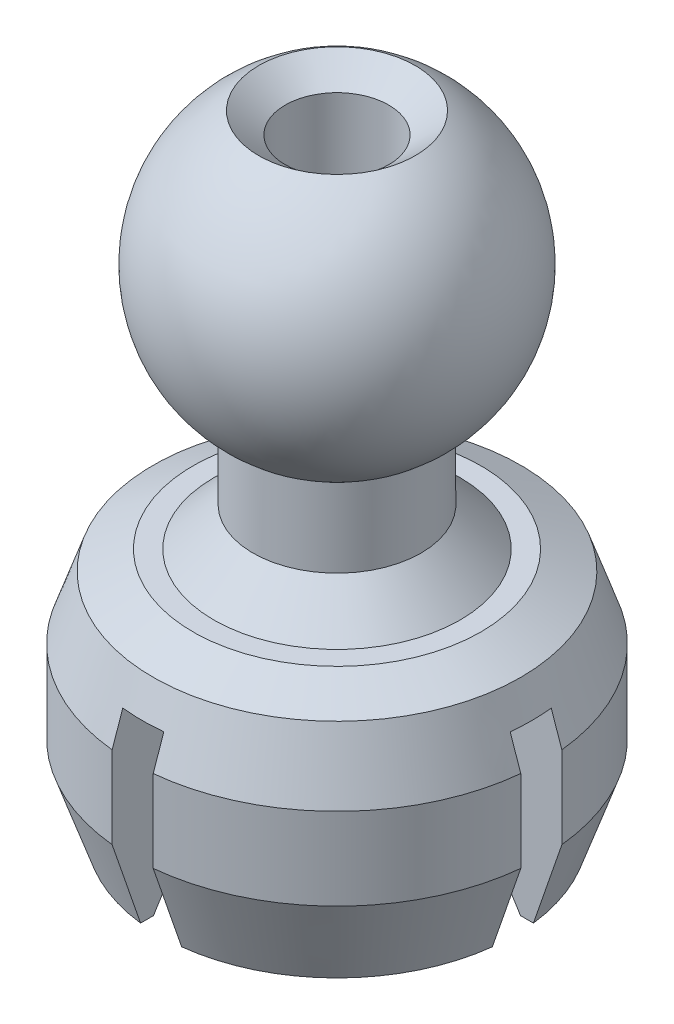
SolidWorks part; units mm, degrees
ref_plane "Ebene vorne" through (0, 0, 0) normal (0, 0, 1) x (1, 0, 0)
ref_plane "Ebene oben" through (0, 0, 0) normal (0, 1, 0) x (1, 0, 0)
ref_plane "Ebene rechts" through (0, 0, 0) normal (1, 0, 0) x (0, 0, -1)
sketch "Skizze1" plane through (0, 0, 0) normal (0, 0, 1) x (1, 0, 0)
  line L0 (-4.0937, 16.8678) -> (-4.0937, 20.6965) construction
  line L1 (-10, 3) -> (-10, 15) construction
  line L2 (-10, 15) -> (-6, 15) construction
  line L3 (0, 15) -> (0, 3) construction
  line L5 (-2.5187, 34.0815) -> (-2.5187, 15.5322)
  line L6 (0, 3) -> (-6, 3) construction
  line L7 (-6, 3) -> (-10, 3) construction
  line L8 (-10, 3) -> (-10, 15) construction
  line L9 (-10, 15) -> (-6, 15) construction
  line L10 (0, 15) -> (0, 18) construction
  line L13 (-6, 3) -> (-10, 3)
  line L14 (-10, 3) -> (-10, 15)
  line L15 (-10, 15) -> (-6, 15)
  line L17 (-6, 15) -> (-4.0937, 16.8678)
  line L18 (-5.2489, 12.8571) -> (-2.5187, 15.5322)
  line L20 (-4.0937, 16.8678) -> (-4.0937, 20.6965)
  arc A0 (-5.2489, 12.8571) -> (-6, 3) centre (0, 7.5) ccw
  arc A1 (-2.5187, 34.0815) -> (-4.0937, 20.6965) centre (0, 27) ccw
revolve "Rotation1" add sketch "Skizze1" angle 360 about L10
chamfer "Fase1" distance 2 angle 58 1 edges at (6, 3, 0)
chamfer "Fase2" distance 4 angle 19 1 edges at (10, 3, 0)
chamfer "Fase3" distance 4 angle 19 1 edges at (10, 15, 0)
sketch "Skizze2" plane through (0, 3, 0) normal (0, -1, 0) x (1, 0, 0)
  line L0 (-4.5568, 6.8352) -> (-5.9015, 5.8392) construction
  line L3 (0, 0) -> (-10.5828, 0) construction
  line L6 (0, 10.6988) -> (1, 10.6988)
  line L7 (0, 0) -> (0, -10.8154) construction
  line L8 (1, 10.6988) -> (1, 1)
  line L10 (12.9234, 0) -> (12.9234, -1)
  line L12 (12.9234, -1) -> (1, -1)
  line L14 (0, -10.8154) -> (-1, -10.8154)
  line L15 (12.9234, 0) -> (12.9234, 1)
  line L16 (-1, -10.8154) -> (-1, -1)
  line L18 (-10.5828, 0) -> (-10.5828, 1)
  line L20 (-10.5828, 1) -> (-1, 1)
  line L21 (12.9234, 1) -> (1, 1)
  line L23 (0, -10.8154) -> (1, -10.8154)
  line L25 (1, -10.8154) -> (1, -1)
  line L27 (-10.5828, 0) -> (-10.5828, -1)
  line L29 (-10.5828, -1) -> (-1, -1)
  line L31 (0, 10.6988) -> (-1, 10.6988)
  line L33 (-1, 10.6988) -> (-1, 1)
extrude "Schnitt-Linear austragen1" cut sketch "Skizze2" against normal blind 9.5
chamfer "Fase4" distance 1 angle 45 1 edges at (8.6227, 15, 0)
chamfer "Fase5" distance 1.5 angle 58 1 edges at (2.5187, 34.0815, 0)
